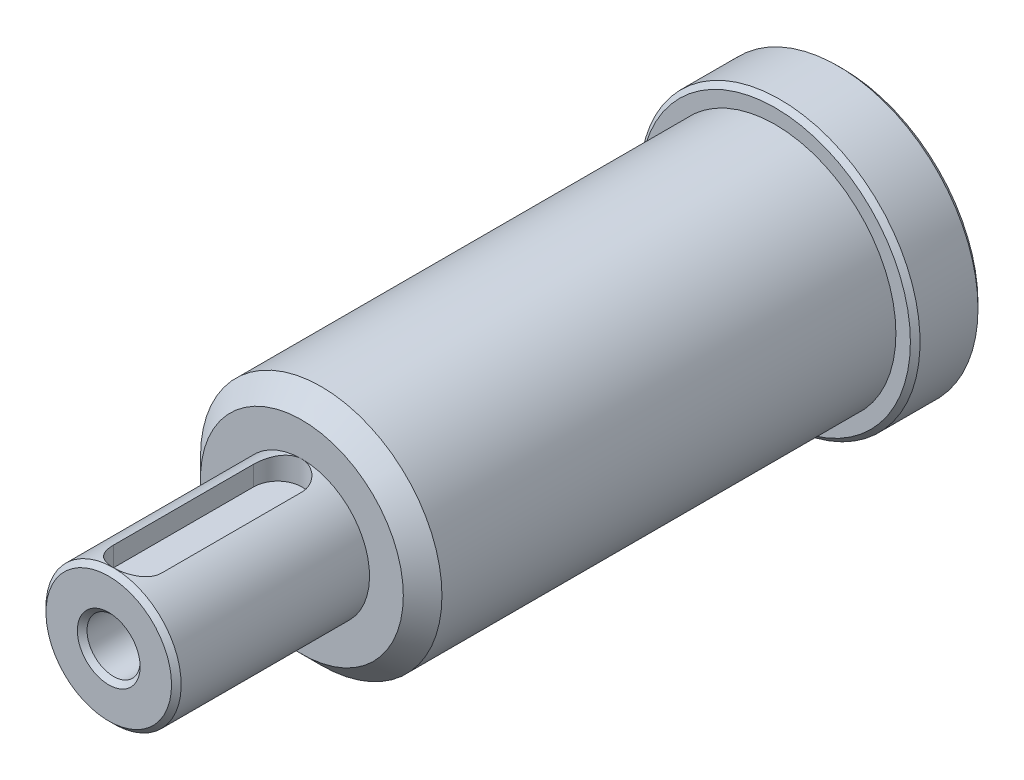
SolidWorks part; units mm, degrees
ref_plane "前视基准面" through (0, 0, 0) normal (0, 0, 1) x (1, 0, 0)
ref_plane "上视基准面" through (0, 0, 0) normal (0, 1, 0) x (1, 0, 0)
ref_plane "右视基准面" through (0, 0, 0) normal (1, 0, 0) x (0, 0, -1)
sketch "草图1" plane through (0, 0, 0) normal (0, 0, 1) x (1, 0, 0)
  circle A0 centre (0, 0) radius 12.5
  dimension "D1" = 25
extrude "拉伸1" add sketch "草图1" along normal blind 56
sketch "草图4" plane through (0, 0, 56) normal (0, 0, 1) x (1, 0, 0)
  circle A0 centre (0, 0) radius 7
  dimension "D1" = 14
extrude "拉伸2" add sketch "草图4" against normal blind 3
sketch "草图7" plane through (0, 0, 56) normal (0, 0, 1) x (1, 0, 0)
  circle A0 centre (0, 0) radius 7
extrude "拉伸3" add sketch "草图7" along normal blind 20
chamfer "倒角1" distance 2 angle 45 1 edges at (12.5, 0, 56)
sketch "草图8" plane through (0, 0, 0) normal (0, 0, -1) x (-1, 0, 0)
  circle A0 centre (0, 0) radius 7
extrude "切除-拉伸3" cut sketch "草图8" against normal blind 33.5
sketch "草图9" plane through (0, 0, 0) normal (0, 0, -1) x (-1, 0, 0)
  circle A0 centre (0, 0) radius 12.5
  circle A1 centre (0, 0) radius 14.5
extrude "拉伸4" add sketch "草图9" against normal blind 7
sketch "草图10" plane through (0, 0, 76) normal (0, 0, 1) x (1, 0, 0)
  circle A0 centre (0, 0) radius 2.75
  dimension "D1" = 5.5
extrude "切除-拉伸4" cut sketch "草图10" against normal through all
ref_plane "基准面1" through (0, 7, 0) normal (0, 1, 0) x (-1, 0, 0)
sketch "草图11" plane through (0, 7, 0) normal (0, 1, 0) x (-1, 0, 0)
  line L0 (10.5, 56) -> (-10.5, 56) construction
  line L1 (7, 76) -> (-7, 76) construction
  line L2 (-2.5, 73) -> (-2.5, 58.5)
  line L3 (2.5, 73) -> (2.5, 58.5)
  arc A0 (2.5, 73) -> (-2.5, 73) centre (0, 73) ccw
  arc A1 (-2.5, 58.5) -> (2.5, 58.5) centre (0, 58.5) ccw
  dimension "D1" = 5
  dimension "D2" = 2.5
  dimension "D3" = 5
  dimension "D4" = 3
extrude "切除-拉伸5" cut sketch "草图11" against normal blind 2.5
sketch "草图12" plane through (0, 0, 0) normal (0, 0, -1) x (-1, 0, 0)
  line L1 (-2.5, 9) -> (2.5, 9)
  line L2 (-2.5, 9) -> (-2.5, 4.5743)
  line L3 (-2.5, 4.5743) -> (2.5, 4.5743)
  line L4 (2.5, 9) -> (2.5, 4.5743)
extrude "切除-拉伸6" cut sketch "草图12" against normal blind 30
chamfer "倒角2" distance 0.5 angle 45 3 edges at (-14.5, 0, 7) (-14.5, 0, 0) (0, -7, 0)
chamfer "倒角3" distance 0.5 angle 45 1 edges at (7, 0, 76)
chamfer "倒角4" distance 0.5 angle 45 1 edges at (2.75, 0, 76)
chamfer "倒角5" distance 0.5 angle 45 1 edges at (-2.75, 0, 33.5)
fillet "圆角1" radius 1 1 edges at (-7, 0, 33.5)
